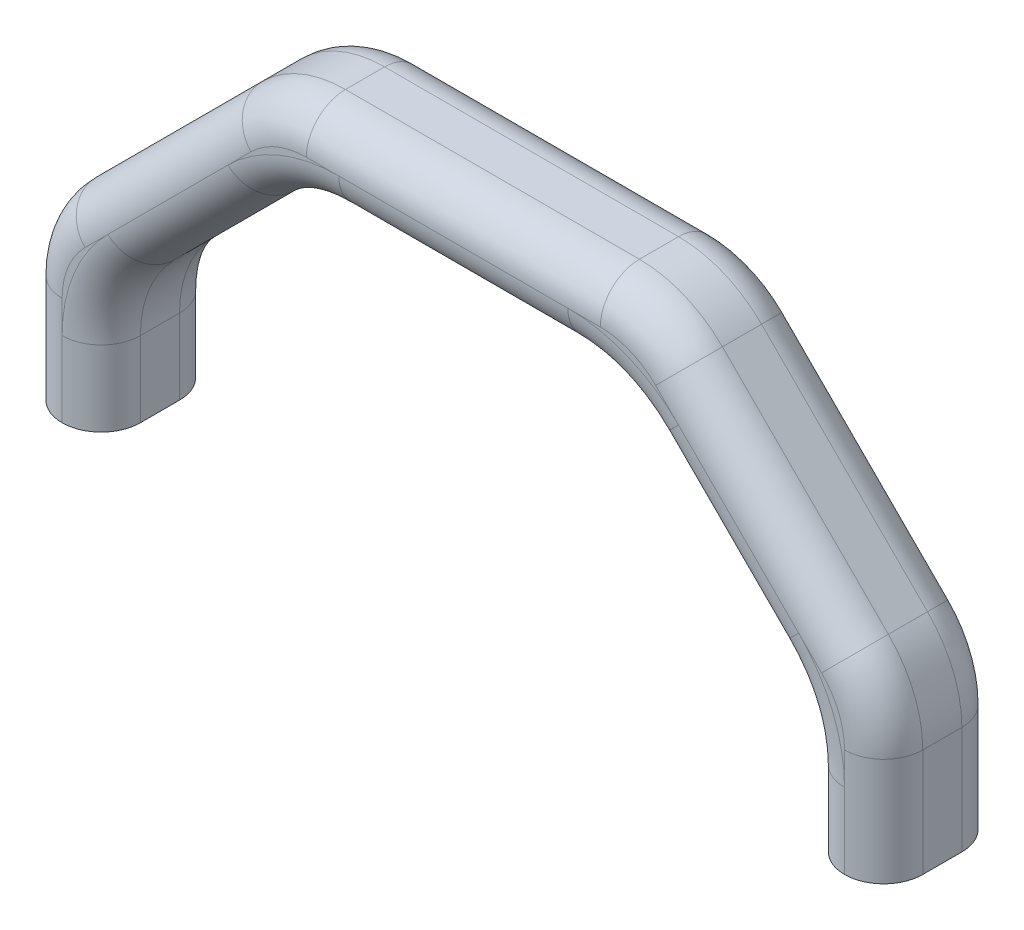
SolidWorks part; units mm, degrees
ref_plane "Plan de face" through (0, 0, 0) normal (0, 0, 1) x (1, 0, 0)
ref_plane "Plan de dessus" through (0, 0, 0) normal (0, 1, 0) x (1, 0, 0)
ref_plane "Plan de droite" through (0, 0, 0) normal (1, 0, 0) x (0, 0, -1)
sketch "Esquisse1" plane through (0, 0, 0) normal (0, 0, 1) x (1, 0, 0)
  line L3 (100, 0) -> (110, 0)
  line L8 (0, 0) -> (0, 20)
  line L9 (0, 20) -> (30, 50)
  line L11 (0, 0) -> (10, 0)
  line L12 (30, 50) -> (80, 50)
  line L14 (80, 50) -> (110, 20)
  line L15 (110, 20) -> (110, 0)
  line L16 (100, 0) -> (100, 15.8579)
  line L17 (100, 15.8579) -> (75.8579, 40)
  line L19 (75.8579, 40) -> (34.1421, 40)
  line L21 (34.1421, 40) -> (10, 15.8579)
  line L22 (10, 15.8579) -> (10, 0)
  point P1 (5, 0)
  point P4 (91.6683, 50)
  point P9 (24.385, 28.0868)
  point P10 (105, 0)
  point P14 (92.4143, 33.1259)
  point P17 (20, 34.5894)
  point P19 (86.8976, 22.4058)
  point P20 (100, 15.6599)
  point P21 (10, 15.6599)
  point P22 (14.7959, 24.2456)
  point P23 (91.9789, 20)
  point P24 (100, 14.4334)
  point P25 (77.9616, 25.7349)
  point P26 (100, -2.9131)
  point P27 (0, 0)
  point P28 (100, 9.5273)
  point P29 (103.9957, 28.5373)
  point P30 (85, 27.4766)
  point P31 (90.5864, 34.6111)
  point P32 (100, 20)
  point P33 (10, 20)
  dimension "D1" = 50
  dimension "D2" = 10
  dimension "D3" = 40
  dimension "D4" = 20
  dimension "D5" = 20
  dimension "D6" = 100
  dimension "D7" = 10
  dimension "D8" = 135
  dimension "D9" = 135
  dimension "D10" = 10
  dimension "D11" = 10
extrude "Boss.-Extru.1" add sketch "Esquisse1" along normal blind 15
fillet "Congé4" radius 15 8 edges at (100, 15.8579, 7.5) (75.8579, 40, 7.5) (34.1421, 40, 7.5) (10, 15.8579, 7.5) (0, 20, 7.5) (30, 50, 7.5) (80, 50, 7.5) (110, 20, 7.5)
fillet "Congé5" radius 5 36 edges at (100, 4.8223, 0) (98.8582, 15.3849, 0) (87.9289, 27.9289, 0) (75.3849, 38.8582, 0) (55, 40, 0) (34.6151, 38.8582, 0) (22.0711, 27.9289, 0) (11.1418, 15.3849, 0) (10, 4.8223, 0) (0, 6.8934, 0) (1.1418, 19.527, 0) (15, 35, 0) (30.473, 48.8582, 0) (55, 50, 0) (79.527, 48.8582, 0) (95, 35, 0) (108.8582, 19.527, 0) (110, 6.8934, 0) (110, 6.8934, 15) (108.8582, 19.527, 15) (95, 35, 15) (79.527, 48.8582, 15) (0, 6.8934, 15) (1.1418, 19.527, 15) (15, 35, 15) (30.473, 48.8582, 15) (10, 4.8223, 15) (11.1418, 15.3849, 15) (22.0711, 27.9289, 15) (34.6151, 38.8582, 15) (55, 40, 15) (75.3849, 38.8582, 15) (100, 4.8223, 15) (98.8582, 15.3849, 15) (55, 50, 15) (87.9289, 27.9289, 15)
sketch "Esquisse2" plane through (0, 0, 0) normal (0, -1, 0) x (-1, 0, 0)
  line L0 (-110, -10) -> (-110, -5) construction
  point P0 (-105, -7.5)
  point P2 (-5, -7.5)
  point P9 (-106.6322, -11.7915)
  dimension "D1" = 100
  dimension "D2" = 5
  dimension "D3" = 7.5
  dimension "D4" = 7.5
hole_wizard "Diamètre du perçage Ø3.2 (3.2)1" positions "Esquisse2" profile "Esquisse3" hole size "Ø3.2" standard "ISO"
sketch "Esquisse3" plane through (105, 0, 7.5) normal (1, 0, 0) x (0, 0, -1)
  line L0 (0, 0) -> (0, 10.9614)
  line L1 (0, 10.9614) -> (1.6, 10)
  line L2 (1.6, 10) -> (1.6, 0)
  line L5 (1.6, 0) -> (0, 0)
  line L10 (0, 10.9614) -> (-1.6, 10) construction
  line L11 (0, -6.35) -> (0, 107.95) construction
  dimension "Diamètre du perçage" = 3.2
  dimension "Profondeur du perçage" = 10
  dimension "Angle de pointe" = 118
